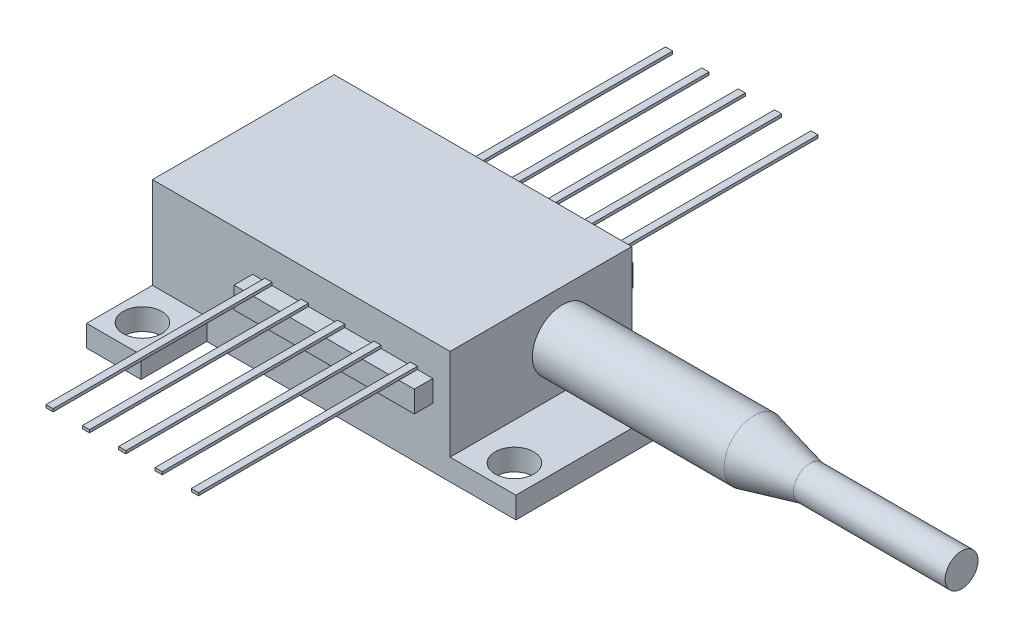
SolidWorks part; units mm, degrees
ref_plane "Front Plane" through (0, 0, 0) normal (0, 0, 1) x (1, 0, 0)
ref_plane "Top Plane" through (0, 0, 0) normal (0, 1, 0) x (1, 0, 0)
ref_plane "Right Plane" through (0, 0, 0) normal (1, 0, 0) x (0, 0, -1)
sketch "Sketch1" plane through (0, 0, 0) normal (0, 1, 0) x (1, 0, 0)
  line L1 (-10.4, -6.35) -> (10.4, -6.35)
  line L2 (-10.4, -6.35) -> (-10.4, 6.35)
  line L3 (-10.4, 6.35) -> (10.4, 6.35)
  line L4 (10.4, -6.35) -> (10.4, 6.35)
  line L5 (-10.4, -6.35) -> (10.4, 6.35) construction
  line L6 (-10.4, 6.35) -> (10.4, -6.35) construction
  point P0 (0, 0)
  dimension "D1" = 12.7
  dimension "D2" = 20.8
extrude "Boss-Extrude1" add sketch "Sketch1" along normal blind 6.4
sketch "Sketch3" plane through (0, 0, 0) normal (0, -1, 0) x (1, 0, 0)
  line L0 (-10.4, 6.35) -> (10.4, 6.35) construction
  line L1 (-10.4, 10.95) -> (-6.6, 10.95)
  line L2 (-10.4, 10.95) -> (-10.4, -10.95)
  line L3 (-10.4, 0) -> (15, 0) construction
  line L4 (15, 6.35) -> (15, -6.35)
  line L5 (-6.6, -6.35) -> (15, -6.35)
  line L6 (-6.6, 10.95) -> (-6.6, 6.35)
  line L7 (-6.6, 6.35) -> (15, 6.35)
  line L8 (-6.6, -10.95) -> (-6.6, -6.35)
  line L9 (-10.4, -10.95) -> (-6.6, -10.95)
  dimension "D1" = 25.4
  dimension "D2" = 10.95
  dimension "D3" = 3.8
extrude "Boss-Extrude2" add sketch "Sketch3" along normal blind 1.5
sketch "Sketch5" plane through (0, -1.5, 0) normal (0, -1, 0) x (1, 0, 0)
  line L0 (15, -6.35) -> (15, 6.35) construction
  line L1 (-10.4, 10.95) -> (-10.4, 6.35) construction
  circle A0 centre (-8.5, 8.95) radius 1.35
  circle A1 centre (13, 4.45) radius 1.35
  dimension "D1" = 2.7
  dimension "D2" = 4.45
  dimension "D3" = 2
  dimension "D4" = 8.95
  dimension "D5" = 1.9
extrude "Cut-Extrude1" cut sketch "Sketch5" against normal through all
mirror "Mirror3" about plane through (0, 0, 0) normal (0, 0, 1) of "Cut-Extrude1"
sketch "Sketch6" plane through (-10.4, 0, 0) normal (-1, 0, 0) x (0, 0, 1)
  line L0 (6.35, 6.4) -> (6.35, 0) construction
  line L1 (10.95, -1.5) -> (-10.95, -1.5) construction
  point P0 (1.85, 3.3)
  dimension "D1" = 4.5
  dimension "D2" = 4.8
ref_point "laser_out"
ref_axis "laser" through (-10.4, 3.3, 1.85) along (-1, 0, 0)
sketch "Sketch7" plane through (10.4, 0, 0) normal (1, 0, 0) x (0, 0, -1)
  line L0 (6.35, 6.4) -> (6.35, 0) construction
  line L1 (6.35, -1.5) -> (-6.35, -1.5) construction
  point P0 (1.5, 3.2)
  dimension "D1" = 4.85
  dimension "D2" = 4.7
ref_point "fiber_out"
ref_plane "Plane2" through (0, 3.2, 0) normal (0, -1, 0) x (-1, 0, 0)
ref_axis "fiber" through (10.4, 3.2, -1.5) along (1, 0, 0)
sketch "Sketch11" plane through (0, 3.2, 0) normal (0, -1, 0) x (-1, 0, 0)
  line L0 (-10.4, 1.5) -> (-10.4, 3.6)
  line L1 (-10.4, -6.35) -> (-10.4, 6.35) construction
  line L2 (-10.4, 3.6) -> (-23.8, 3.6)
  line L3 (-23.8, 3.6) -> (-27.7, 2.65)
  line L4 (-27.7, 2.65) -> (-38.3, 2.65)
  line L5 (-38.3, 2.65) -> (-38.3, 1.5)
  line L6 (-10.4, 1.5) -> (-61.1766, 1.5) construction
  line L7 (-38.3, 1.5) -> (-10.4, 1.5)
  line L9 (-15, 6.35) -> (-15, -6.35) construction
  dimension "D1" = 1.15
  dimension "D2" = 2.1
  dimension "D3" = 8.8
  dimension "D4" = 12.7
  dimension "D5" = 23.3
revolve "Revolve1" add sketch "Sketch11" angle 360 about axis through (10.4, 3.2, -1.5) along (1, 0, 0)
ref_plane "Plane1" through (0, 2.665, 0) normal (0, -1, 0) x (-1, 0, 0)
sketch "Sketch9" plane through (0, 2.665, 0) normal (0, -1, 0) x (-1, 0, 0)
  line L0 (10.4, -6.35) -> (-10.4, -6.35) construction
  line L1 (3.4, -6.35) -> (-9.2, -6.35)
  line L2 (3.4, -6.35) -> (3.4, -7.65)
  line L3 (3.4, -7.65) -> (-9.2, -7.65)
  line L4 (-9.2, -6.35) -> (-9.2, -7.65)
  line L6 (10.4, 6.35) -> (10.4, -6.35) construction
  line L7 (-10.4, -6.35) -> (-10.4, 6.35) construction
  dimension "D1" = 7.65
  dimension "D2" = 1.2
  dimension "D3" = 7
extrude "Boss-Extrude4" add sketch "Sketch9" against normal blind 1.5
sketch "Sketch10" plane through (0, 4.165, 0) normal (0, 1, 0) x (1, 0, 0)
  line L0 (-3.4, -6.35) -> (9.2, -6.35) construction
  line L1 (7.62, -6.35) -> (8.12, -6.35)
  line L2 (7.62, -6.35) -> (7.62, -21.65)
  line L3 (7.62, -21.65) -> (8.12, -21.65)
  line L4 (8.12, -6.35) -> (8.12, -21.65)
  line L5 (7.87, -6.35) -> (7.87, -21.65) construction
  line L6 (10.4, -6.35) -> (10.4, 6.35) construction
  dimension "D1" = 0.5
  dimension "D2" = 21.65
  dimension "D3" = 2.53
extrude "Boss-Extrude5" add sketch "Sketch10" along normal blind 0.2
pattern_linear "LPattern1" count 5 spacing 2.54 along (-1, 0, 0) of "Boss-Extrude5"
mirror "Mirror2" about plane through (0, 0, 0) normal (0, 0, 1) of "Boss-Extrude4", "Boss-Extrude5", "LPattern1"
